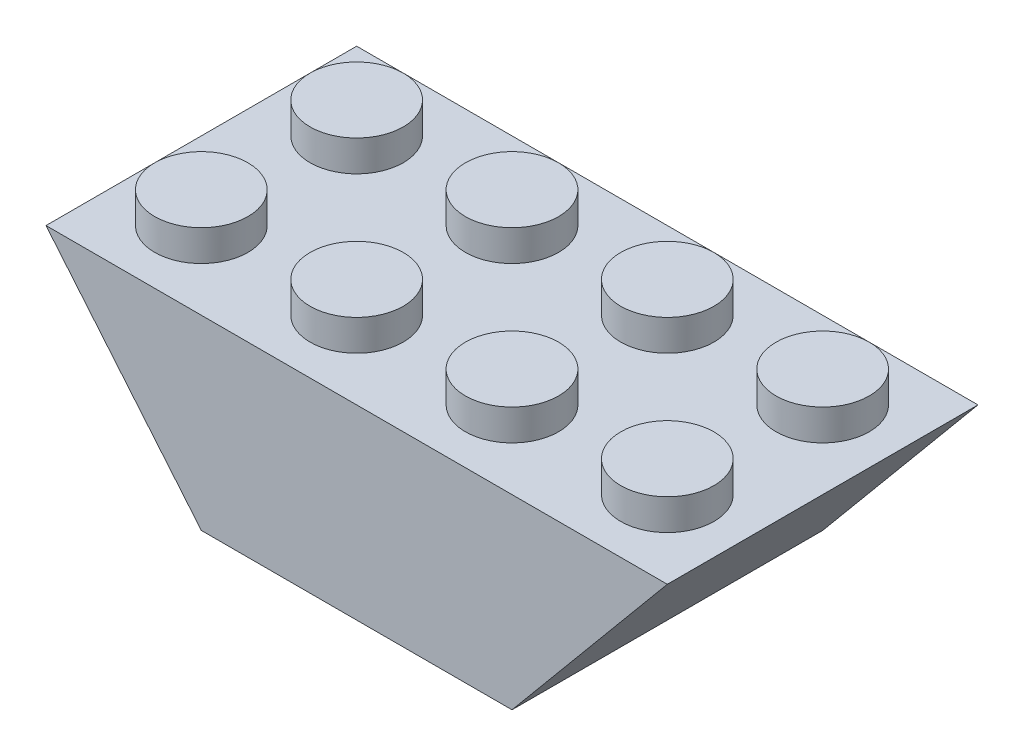
SolidWorks part; units mm, degrees
ref_plane "Front Plane" through (0, 0, 0) normal (0, 0, 1) x (1, 0, 0)
ref_plane "Top Plane" through (0, 0, 0) normal (0, 1, 0) x (1, 0, 0)
ref_plane "Right Plane" through (0, 0, 0) normal (1, 0, 0) x (0, 0, -1)
sketch "Sketch1" plane through (0, 0, 0) normal (0, 0, 1) x (1, 0, 0)
  line L0 (-8, 0) -> (8, 0)
  line L1 (8, 0) -> (16, 9.6)
  line L2 (16, 9.6) -> (-16, 9.6)
  line L3 (-16, 9.6) -> (-8, 0)
  point P4 (0, 0)
  dimension "D1" = 9.6
  dimension "D2" = 16
  dimension "D3" = 32
extrude "Boss-Extrude1" add sketch "Sketch1" along normal blind 16
sketch "Sketch2" plane through (0, 9.6, 0) normal (0, 1, 0) x (1, 0, 0)
  line L0 (-16, -16) -> (-12, -16) construction
  line L1 (16, -16) -> (-16, -16) construction
  line L2 (-12, -16) -> (-12, -12) construction
  circle A0 centre (-12, -12) radius 2.4
  dimension "D1" = 4.8
  dimension "D2" = 4
  dimension "D3" = 4
extrude "Boss-Extrude2" add sketch "Sketch2" along normal blind 1.6
pattern_linear "LPattern1" count 2 spacing 8 along (0, 0, -1) count 4 spacing 8 along (1, 0, 0) of "Boss-Extrude2"
shell "Shell1" thickness 1.6 removed face at (0, 0, 8)
